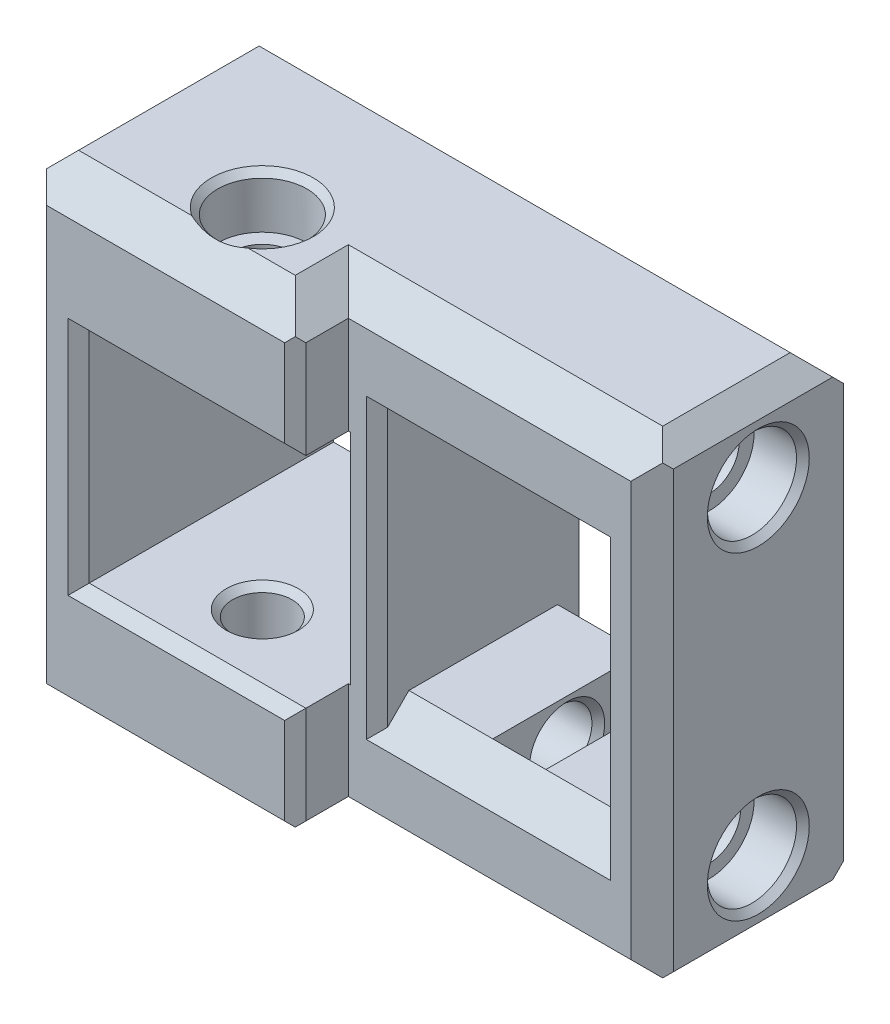
SolidWorks part; units mm, degrees
ref_plane "Front Plane" through (0, 0, 0) normal (0, 0, 1) x (1, 0, 0)
ref_plane "Top Plane" through (0, 0, 0) normal (0, 1, 0) x (1, 0, 0)
ref_plane "Right Plane" through (0, 0, 0) normal (1, 0, 0) x (0, 0, -1)
sketch "Sketch1" plane through (0, 0, 0) normal (0, 0, 1) x (1, 0, 0)
  line L1 (0, 0) -> (68.58, 0)
  line L2 (0, 0) -> (0, 57.15)
  line L3 (0, 57.15) -> (68.58, 57.15)
  line L4 (68.58, 0) -> (68.58, 57.15)
  dimension "D1" = 57.15
  dimension "D2" = 68.58
extrude "Boss-Extrude1" add sketch "Sketch1" along normal blind 31.75
sketch "Sketch2" plane through (0, 0, 31.75) normal (0, 0, 1) x (1, 0, 0)
  line L1 (6.35, 15.494) -> (32.512, 15.494)
  line L2 (6.35, 15.494) -> (6.35, 41.656)
  line L3 (6.35, 41.656) -> (32.512, 41.656)
  line L4 (32.512, 15.494) -> (32.512, 41.656)
  line L5 (35.687, 42.545) -> (62.357, 42.545)
  line L6 (35.687, 42.545) -> (35.687, 14.605)
  line L7 (35.687, 14.605) -> (62.357, 14.605)
  line L8 (62.357, 42.545) -> (62.357, 14.605)
  line L9 (82.1588, 28.575) -> (-8.3557, 28.575) construction
  line L10 (68.58, 57.15) -> (0, 57.15) construction
  line L12 (0, 57.15) -> (0, 0) construction
  point P10 (6.35, 28.575)
  point P13 (62.357, 28.575)
  dimension "D1" = 26.162
  dimension "D2" = 27.94
  dimension "D3" = 3.175
  dimension "D4" = 28.575
  dimension "D5" = 6.35
  dimension "D6" = 26.67
extrude "Cut-Extrude1" cut sketch "Sketch2" against normal through all
sketch "Sketch5" plane through (68.58, 0, 0) normal (1, 0, 0) x (0, 0, -1)
  line L0 (-31.75, 57.15) -> (0, 57.15) construction
  line L1 (-40.1188, 28.575) -> (12.2247, 28.575) construction
  line L3 (0, 0) -> (0, 57.15) construction
  circle A0 centre (-12.7, 47.625) radius 3.556
  circle A1 centre (-12.7, 9.525) radius 3.7293
  dimension "D1" = 7.112
  dimension "D2" = 19.05
  dimension "D3" = 28.575
  dimension "D4" = 38.1
  dimension "D5" = 12.7
extrude "Cut-Extrude2" cut sketch "Sketch5" against normal through all contours A0 | A1
sketch "Sketch6" plane through (68.58, 0, 0) normal (1, 0, 0) x (0, 0, -1)
  line L0 (-21.59, 47.625) -> (-21.59, 12.2127)
  line L1 (-3.81, 47.625) -> (-3.81, 6.8373)
  arc A0 (-21.59, 47.625) -> (-3.81, 47.625) centre (-12.7, 47.625) cw
  arc A2 (-3.81, 6.8373) -> (-21.59, 12.2127) centre (-12.7, 9.525) cw
  dimension "D1" = 8.89
extrude "Cut-Extrude3" cut sketch "Sketch6" against normal blind 6.35 from offset 16.51 offset against normal yes
sketch "Sketch7" plane through (68.58, 0, 0) normal (1, 0, 0) x (0, 0, -1)
  circle A0 centre (-12.7, 47.625) radius 5.334
  circle A1 centre (-12.7, 9.525) radius 5.334
  dimension "D1" = 10.668
extrude "Cut-Extrude4" cut sketch "Sketch7" against normal blind 5.842
sketch "Sketch9" plane through (0, 0, 0) normal (-1, 0, 0) x (0, 0, 1)
  line L1 (16.0729, 53.467) -> (9.3271, 53.467)
  line L2 (9.3271, 53.467) -> (5.9542, 47.625)
  line L3 (5.9542, 47.625) -> (9.3271, 41.783)
  line L4 (9.3271, 41.783) -> (16.0729, 41.783)
  line L5 (16.0729, 41.783) -> (19.4458, 47.625)
  line L6 (19.4458, 47.625) -> (16.0729, 53.467)
  line L7 (16.0729, 15.367) -> (9.3271, 15.367)
  line L8 (9.3271, 15.367) -> (5.9542, 9.525)
  line L9 (5.9542, 9.525) -> (9.3271, 3.683)
  line L10 (9.3271, 3.683) -> (16.0729, 3.683)
  line L11 (16.0729, 3.683) -> (19.4458, 9.525)
  line L12 (19.4458, 9.525) -> (16.0729, 15.367)
  circle A0 centre (12.7, 47.625) radius 5.842 construction
  circle A1 centre (12.7, 9.525) radius 5.842 construction
  dimension "D1" = 11.684
extrude "Cut-Extrude5" cut sketch "Sketch9" against normal blind 7.62
sketch "Sketch10" plane through (0, 57.15, 0) normal (0, 1, 0) x (1, 0, 0)
  line L1 (68.58, -31.75) -> (32.258, -31.75)
  line L2 (68.58, -31.75) -> (68.58, -25.4)
  line L3 (68.58, -25.4) -> (32.258, -25.4)
  line L4 (32.258, -31.75) -> (32.258, -25.4)
  dimension "D1" = 6.35
  dimension "1.3" = 36.322
extrude "Cut-Extrude6" cut sketch "Sketch10" against normal through all
sketch "Sketch12" plane through (0, 15.494, 0) normal (0, 1, 0) x (1, 0, 0)
  line L0 (6.35, -31.75) -> (32.258, -31.75) construction
  line L1 (6.35, 0) -> (6.35, -31.75) construction
  circle A0 centre (19.431, -22.86) radius 3.556
  dimension "D3" = 7.112
  dimension "D1" = 8.89
  dimension "D2" = 13.081
extrude "Cut-Extrude7" cut sketch "Sketch12" against normal through all both and the other way through all contours A0
sketch "Sketch13" plane through (0, 57.15, 0) normal (0, 1, 0) x (1, 0, 0)
  circle A0 centre (19.431, -22.86) radius 5.334
  dimension "D1" = 10.668
extrude "Cut-Extrude8" cut sketch "Sketch13" against normal blind 6.35 contours A0
sketch "Sketch14" plane through (0, 0, 0) normal (0, -1, 0) x (1, 0, 0)
  line L0 (0, 31.75) -> (32.258, 31.75) construction
  line L1 (22.8039, 28.702) -> (16.0581, 28.702)
  line L2 (16.0581, 28.702) -> (12.6852, 22.86)
  line L3 (12.6852, 22.86) -> (16.0581, 17.018)
  line L4 (16.0581, 17.018) -> (22.8039, 17.018)
  line L5 (22.8039, 17.018) -> (26.1768, 22.86)
  line L6 (26.1768, 22.86) -> (22.8039, 28.702)
  circle A0 centre (19.431, 22.86) radius 5.842 construction
  dimension "D1" = 11.684
extrude "Cut-Extrude9" cut sketch "Sketch14" against normal blind 7.62
chamfer "Chamfer1" distance 0.762 angle 45 27 edges at (0, 15.367, 12.7) (0, 12.446, 7.6407) (0, 6.604, 7.6407) (0, 3.683, 12.7) (0, 6.604, 17.7593) (0, 12.446, 17.7593) (0, 44.704, 17.7593) (0, 41.783, 12.7) (0, 44.704, 7.6407) (0, 50.546, 7.6407) (0, 53.467, 12.7) (0, 50.546, 17.7593) (19.431, 0, 28.702) (14.3717, 0, 25.781) (14.3717, 0, 19.939) (19.431, 0, 17.018) (24.4903, 0, 19.939) (24.4903, 0, 25.781) (15.875, 41.656, 22.86) (19.431, 57.15, 28.194) (22.987, 15.494, 22.86) (68.58, 9.525, 7.366) (68.58, 47.625, 7.366) (52.07, 9.525, 16.4293) (45.72, 9.525, 16.4293) (45.72, 47.625, 16.256) (52.07, 47.625, 16.256)
chamfer "Chamfer3" distance 3.81 angle 45 4 edges at (49.022, 14.605, 0) (49.022, 42.545, 0) (49.022, 14.605, 25.4) (49.022, 42.545, 25.4)
chamfer "Chamfer5" distance 1.27 angle 45 13 edges at (32.512, 28.575, 0) (19.431, 41.656, 0) (6.35, 28.575, 0) (19.431, 15.494, 0) (62.357, 28.575, 0) (35.687, 28.575, 0) (62.357, 28.575, 25.4) (35.687, 28.575, 25.4) (19.304, 15.494, 31.75) (6.35, 28.575, 31.75) (19.304, 41.656, 31.75) (32.258, 49.403, 31.75) (32.258, 7.747, 31.75)
chamfer "Chamfer6" distance 2.54 angle 45 8 edges at (0, 57.15, 15.875) (68.58, 57.15, 12.7) (0, 0, 15.875) (68.58, 0, 12.7) (0, 28.575, 0) (0, 28.575, 31.75) (68.58, 28.575, 25.4) (68.58, 28.575, 0)
chamfer "Chamfer9" distance 3.81 angle 45 6 edges at (49.149, 57.15, 25.4) (32.258, 57.15, 27.94) (16.764, 57.15, 31.75) (16.764, 0, 31.75) (32.258, 0, 27.94) (49.149, 0, 25.4)
chamfer "Chamfer10" distance 6.35 angle 45 2 edges at (34.29, 57.15, 0) (34.29, 0, 0)
